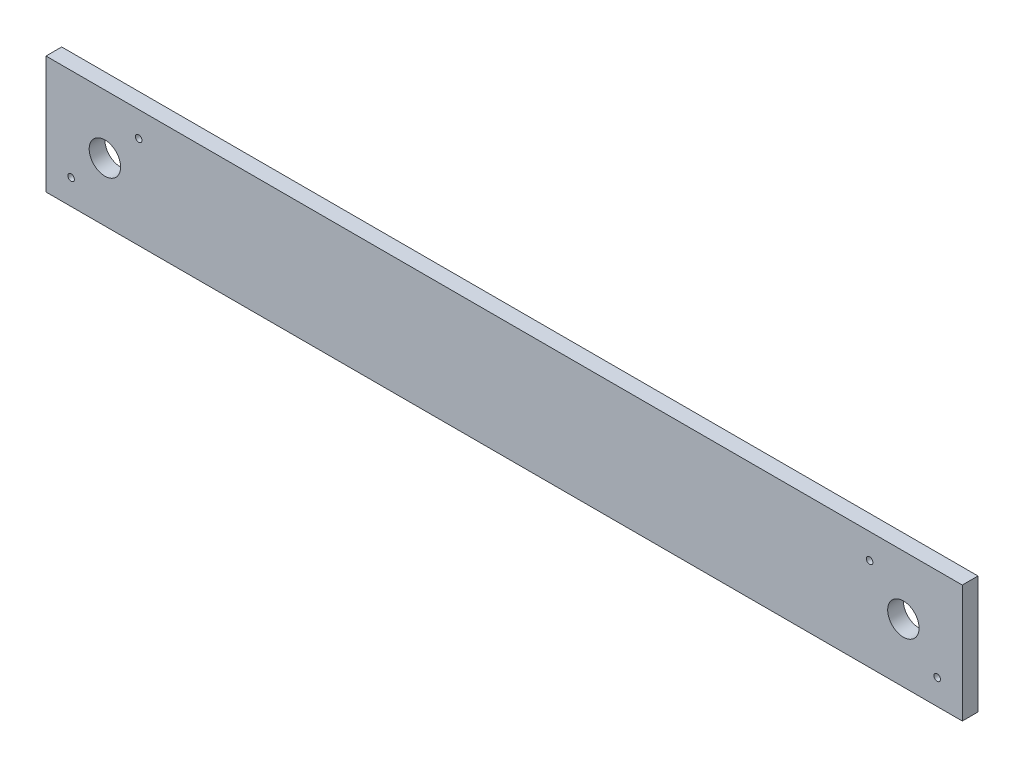
SolidWorks part; units mm, degrees
ref_plane "Alzado" through (0, 0, 0) normal (0, 0, 1) x (1, 0, 0)
ref_plane "Planta" through (0, 0, 0) normal (0, 1, 0) x (1, 0, 0)
ref_plane "Vista lateral" through (0, 0, 0) normal (1, 0, 0) x (0, 0, -1)
sketch "Croquis1" plane through (0, 0, 0) normal (0, 0, 1) x (1, 0, 0)
  line L1 (-350, -45) -> (0, -45)
  line L2 (-350, -45) -> (-350, 0)
  line L3 (-350, 0) -> (0, 0)
  line L4 (0, -45) -> (0, 0)
  dimension "D1" = 350
  dimension "D2" = 45
extrude "Saliente-Extruir1" add sketch "Croquis1" along normal blind 6 contours L3 L4 L1 L2
sketch "Croquis2" plane through (0, 0, 6) normal (0, 0, 1) x (1, 0, 0)
  line L0 (-350, -45) -> (-350, 0) construction
  line L1 (0, -45) -> (0, 0) construction
  line L2 (-350, -45) -> (0, -45) construction
  line L3 (-340.4047, -35.4047) -> (-314.5953, -9.5953) construction
  line L4 (-35.4047, -9.5953) -> (-9.5953, -35.4047) construction
  line L5 (-350, 0) -> (0, 0) construction
  circle A0 centre (-327.5, -22.5) radius 6
  circle A1 centre (-22.5, -22.5) radius 6
  circle A2 centre (-327.5, -22.5) radius 18.25 construction
  circle A4 centre (-314.5953, -9.5953) radius 1.25
  circle A5 centre (-340.4047, -35.4047) radius 1.25
  circle A6 centre (-22.5, -22.5) radius 18.25 construction
  circle A7 centre (-35.4047, -9.5953) radius 1.25
  circle A8 centre (-9.5953, -35.4047) radius 1.25
  dimension "D1" = 12
  dimension "D2" = 12
  dimension "D7" = 36.5
  dimension "D9" = 2.5
  dimension "D10" = 2.5
  dimension "D11" = 36.5
  dimension "D13" = 2.5
  dimension "D14" = 2.5
  dimension "D3" = 22.5
  dimension "D4" = 22.5
  dimension "D5" = 22.5
  dimension "D6" = 22.5
  dimension "D8" = 45
  dimension "D12" = 45
extrude "Cortar-Extruir1" cut sketch "Croquis2" against normal through all
